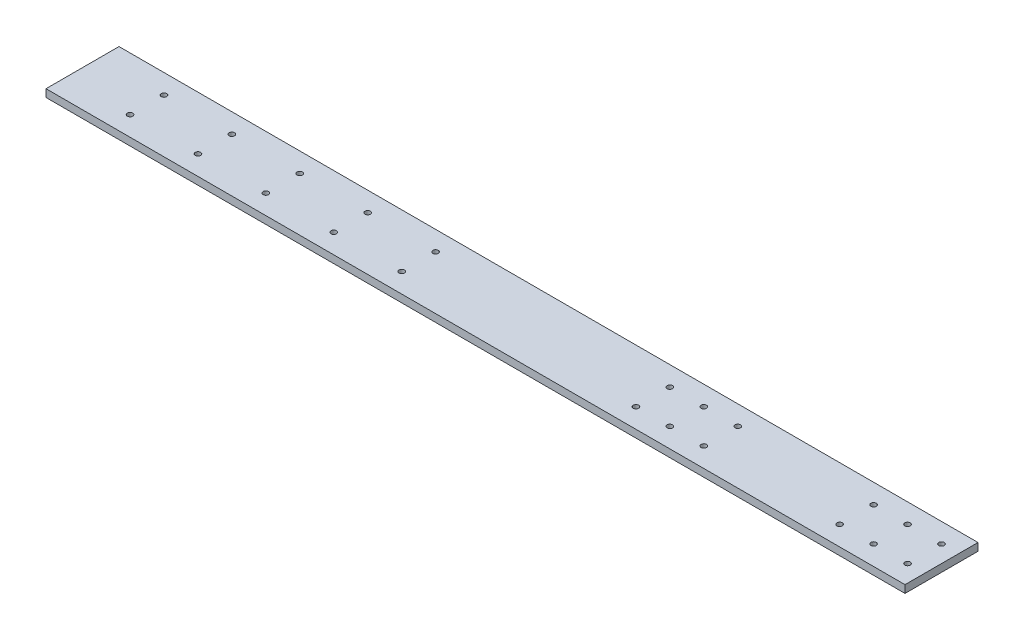
SolidWorks part; units mm, degrees
ref_plane "Front Plane" through (0, 0, 0) normal (0, 0, 1) x (1, 0, 0)
ref_plane "Top Plane" through (0, 0, 0) normal (0, 1, 0) x (1, 0, 0)
ref_plane "Right Plane" through (0, 0, 0) normal (1, 0, 0) x (0, 0, -1)
sketch "Sketch1" plane through (0, 0, 0) normal (0, 1, 0) x (1, 0, 0)
  line L0 (-253, 0) -> (-17, 0) construction
  line L1 (-253, -21.5) -> (253, -21.5)
  line L2 (-253, -21.5) -> (-253, 21.5)
  line L3 (-253, 21.5) -> (253, 21.5)
  line L4 (253, -21.5) -> (253, 21.5)
  line L5 (-253, -21.5) -> (253, 21.5) construction
  line L6 (-253, 21.5) -> (253, -21.5) construction
  line L7 (-17, -35) -> (-17, 35) construction
  line L8 (-17, 21.5) -> (-17, -21.5) construction
  circle A0 centre (-215, 10) radius 1.6
  circle A2 centre (-175, 10) radius 1.6
  circle A3 centre (-135, 10) radius 1.6
  circle A4 centre (-95, 10) radius 1.6
  circle A5 centre (-55, 10) radius 1.6
  circle A8 centre (-175, -10) radius 1.6
  circle A9 centre (-135, -10) radius 1.6
  circle A10 centre (-95, -10) radius 1.6
  circle A11 centre (-55, -10) radius 1.6
  circle A14 centre (-215, -10) radius 1.6
  circle A15 centre (223, 10) radius 1.6
  circle A16 centre (103, 10) radius 1.6
  circle A17 centre (103, -10) radius 1.6
  circle A18 centre (223, -10) radius 1.6
  circle A19 centre (123, -10) radius 1.6
  circle A20 centre (123, 10) radius 1.6
  circle A21 centre (243, 10) radius 1.6
  circle A22 centre (243, -10) radius 1.6
  circle A23 centre (83, -10) radius 1.6
  circle A24 centre (83, 10) radius 1.6
  circle A25 centre (203, 10) radius 1.6
  circle A26 centre (203, -10) radius 1.6
  point P0 (0, 0)
  dimension "D4" = 3.2
  dimension "D5" = 5
  dimension "D1" = 506
  dimension "D2" = 43
  dimension "D3" = 10
  dimension "D7" = 38
  dimension "D8" = 30
  dimension "D9" = 240
  dimension "D6" = 2
  dimension "D10" = 2
  dimension "D11" = 2
  dimension "D12" = 2
  dimension "D13" = 2
extrude "Boss-Extrude1" add sketch "Sketch1" along normal blind 4.5
